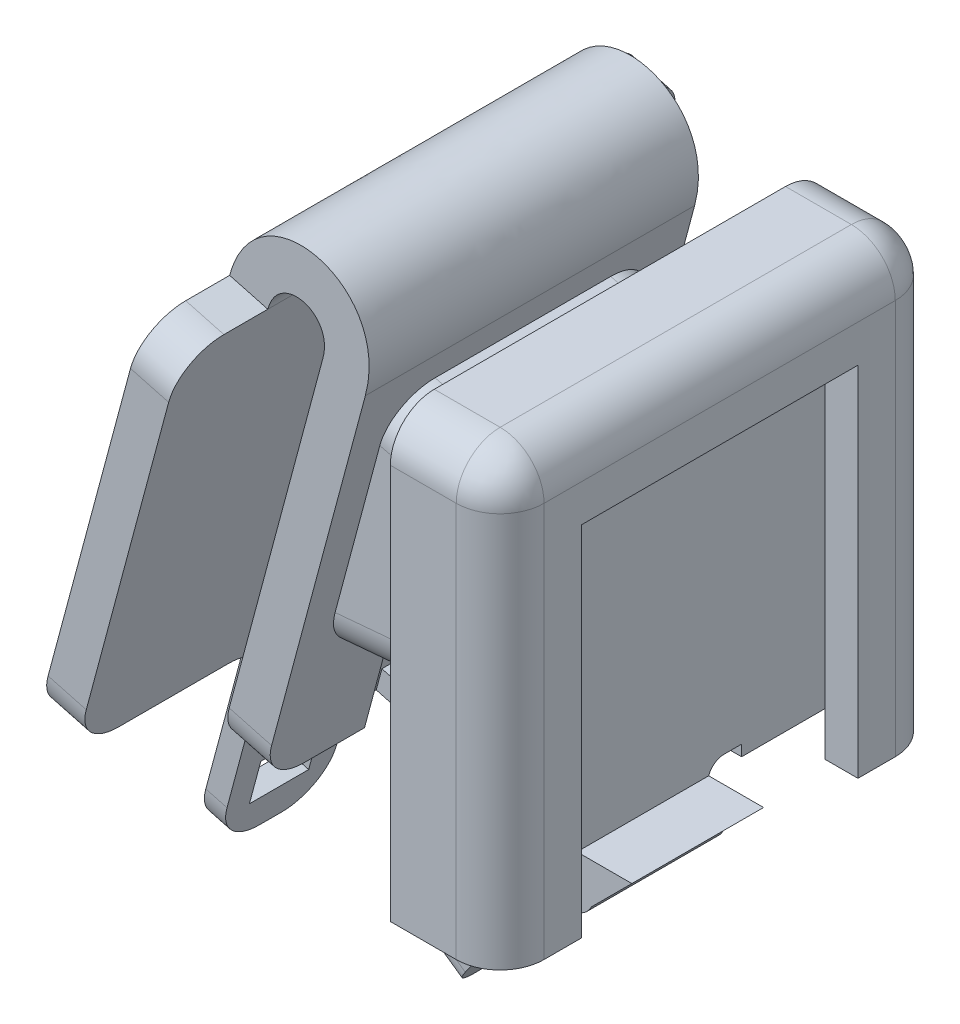
SolidWorks part; units mm, degrees
ref_plane "Front Plane" through (0, 0, 0) normal (0, 0, 1) x (1, 0, 0)
ref_plane "Top Plane" through (0, 0, 0) normal (0, 1, 0) x (1, 0, 0)
ref_plane "Right Plane" through (0, 0, 0) normal (1, 0, 0) x (0, 0, -1)
ref_axis "Axis1" through (-33.0333, 0, 0) along (1, 0, 0)
ref_axis "Axis2" through (0, 24.5224, 0) along (0, -1, 0)
ref_axis "Axis3" through (0, 0, -30.7663) along (0, 0, 1)
sketch "Sketch1" plane through (0, 0, 0) normal (1, 0, 0) x (0, 0, -1)
  line L2 (-10, -10) -> (-10, 10)
  line L4 (10, -10) -> (10, 10)
  line L5 (-10, -10) -> (10, 10) construction
  line L6 (-10, 10) -> (10, -10) construction
  line L8 (-10, 10) -> (10, 10)
  line L19 (0, -10) -> (0, 0) construction
  line L20 (-10, -10) -> (-4.5, -10)
  line L21 (-4.5, -10) -> (-4.5, -9.5)
  line L22 (-4.5, -9.5) -> (-3, -9.5)
  line L23 (-3, -9.5) -> (-3, -10)
  line L24 (-3, -10) -> (3, -10)
  line L25 (3, -10) -> (3, -9.5)
  line L26 (3, -9.5) -> (4.5, -9.5)
  line L27 (4.5, -9.5) -> (4.5, -10)
  line L28 (4.5, -10) -> (10, -10)
  point P0 (0, 0)
  point P25 (0, -10)
  dimension "D1" = 20
  dimension "D2" = 20
  dimension "D6" = 9
  dimension "D7" = 1.5
  dimension "D8" = 0.5
extrude "Boss-Extrude1" add sketch "Sketch1" along normal blind 1.5
fillet "Fillet7" radius 0.75 2 edges at (0.75, -9.5, -3) (0.75, -9.5, 3)
sketch "Sketch3" plane through (1.5, 0, 0) normal (1, 0, 0) x (0, 0, -1)
  line L2 (-10, 10) -> (-10, -10)
  line L4 (10, 10) -> (10, -10)
  line L6 (-8.5, 8.5) -> (-8.5, -10)
  line L10 (8.5, -10) -> (8.5, 8.5)
  line L14 (-10, -10) -> (-4.5, -10) construction
  line L15 (-10, -10) -> (-8.5, -10)
  line L16 (4.5, -10) -> (10, -10) construction
  line L17 (8.5, -10) -> (10, -10)
  line L18 (-8.5, 8.5) -> (8.5, 8.5)
  line L19 (0, 8.5) -> (0, 10) construction
  line L20 (10, 10) -> (-10, 10) construction
  line L21 (-10, 10) -> (10, 10)
  dimension "D1" = 1.5
  dimension "D2" = 1.5
extrude "Boss-Extrude2" add sketch "Sketch3" along normal blind 2
sketch "Sketch5" plane through (3.5, 0, 0) normal (1, 0, 0) x (0, 0, -1)
  line L0 (-10, 10) -> (-10, -10)
  line L2 (10, -10) -> (10, 10)
  line L5 (6.3, 6.3) -> (6.3, -10)
  line L7 (-6.3, -10) -> (-6.3, 6.3)
  line L12 (-8.5, -10) -> (-4.5, -10) construction
  line L13 (4.5, -10) -> (8.5, -10) construction
  line L14 (10, -10) -> (10, 10) construction
  line L15 (-10, 10) -> (10, 10)
  line L16 (6.3, 6.3) -> (-6.3, 6.3)
  line L17 (-6.3, -10) -> (-10, -10)
  line L18 (6.3, -10) -> (10, -10)
  line L19 (0, 6.3) -> (0, 10) construction
  dimension "D1" = 3.7
extrude "Boss-Extrude3" add sketch "Sketch5" along normal blind 1.5
sketch "Sketch9" plane through (0, 0, 0) normal (0, 0, 1) x (1, 0, 0)
  line L14 (0, -10) -> (4, -10)
  line L15 (5, -10) -> (0, -10) construction
  line L16 (4, -10) -> (2.1589, -11.8411)
  line L17 (2.1589, -11.8411) -> (2.1589, -12.4078)
  line L18 (2.1589, -12.4078) -> (-0.1693, -12.4078)
  line L19 (-0.1693, -12.4078) -> (-4.1619, -18.1099)
  line L20 (-4.1619, -18.1099) -> (-5.8002, -16.9628)
  line L21 (-5.8002, -16.9628) -> (-0.9248, -10)
  line L24 (-0.9248, -10) -> (0, -10)
  dimension "D2" = 0.9248
  dimension "D8" = 4
  dimension "D9" = 45
  dimension "D10" = 125
  dimension "D13" = 8.5
  dimension "D14" = 2
extrude "Boss-Extrude5" add sketch "Sketch9" along normal up to vertex (3 mm away) and the other way up to vertex (3 mm away) contours L14 L16 L17 L18 L19 L20 L21 L24 up to point (1.5, -10, 3) other way up to point (1.5, -10, -3)
sketch "Sketch6" plane through (0, 0, 0) normal (0, 0, 1) x (1, 0, 0)
  line L0 (0, 0) -> (-7, 0) construction
  line L1 (0, 10) -> (0, -10) construction
  line L2 (-7, 0) -> (-7, -1) construction
  line L3 (-4.6059, 7.9348) -> (-9.3941, -9.9348) construction
  line L4 (-10.36, -9.676) -> (-8.4282, -10.1936)
  line L5 (-10.36, -9.676) -> (-5.5718, 8.1936)
  line L6 (-5.5718, 8.1936) -> (-3.64, 7.676)
  line L7 (-8.4282, -10.1936) -> (-3.64, 7.676)
  dimension "D1" = 2
  dimension "D2" = 9.25
  dimension "D3" = 75
  dimension "D4" = 1
  dimension "D5" = 7
  dimension "D6" = 9.25
extrude "Boss-Extrude4" add sketch "Sketch6" along normal blind 7.5 and the other way blind 7.5 separate body
sketch "Sketch7" plane through (-5.3152, 1.4242, 0) normal (0.9659, -0.2588, 0) x (0, 0, -1)
  line L0 (0, -12.0277) -> (0, 6.4723) construction
  line L1 (7.5, -12.0277) -> (-7.5, -12.0277) construction
  line L2 (7.5, 6.4723) -> (-7.5, 6.4723) construction
  line L3 (-6, -6.7777) -> (6, -6.7777)
  line L4 (-6, -6.7777) -> (-6, 5.2223)
  line L5 (-6, 5.2223) -> (6, 5.2223)
  line L6 (6, -6.7777) -> (6, 5.2223)
  line L7 (-6, -6.7777) -> (6, 5.2223) construction
  line L8 (-6, 5.2223) -> (6, -6.7777) construction
  point P8 (0, -0.7777)
  point P13 (0, -2.7777)
  dimension "D1" = 12
  dimension "D2" = 12
  dimension "D3" = 2
sketch "Sketch8" plane through (0, 0, 0) normal (-1, 0, 0) x (0, 0, 1)
  line L0 (0, 0) -> (0, 0.5) construction
  line L2 (-6, -4.5) -> (6, -4.5)
  line L3 (-6, -4.5) -> (-6, 5.5)
  line L4 (-6, 5.5) -> (6, 5.5)
  line L5 (6, -4.5) -> (6, 5.5)
  line L6 (-6, -4.5) -> (6, 5.5) construction
  line L7 (-6, 5.5) -> (6, -4.5) construction
  dimension "D1" = 12
  dimension "D2" = 0.5
  dimension "D3" = 10
loft "Loft1" add profiles "Sketch7", "Sketch8" connector at (-7.0694, -5.1225, 6) connector at (0, -4.5, 6)
ref_plane "Plane1" through (1.3516, 5.0444, 0) normal (0.2588, 0.9659, 0) x (0, 0, 1)
ref_plane "Plane2" through (-9.7584, 2.6148, 0) normal (-0.9659, 0.2588, 0) x (0, 0, 1)
sketch "Sketch11" plane through (-9.7584, 2.6148, 0) normal (-0.9659, 0.2588, 0) x (0, 0, 1)
  line L0 (0, 6.4723) -> (0, -12.0277) construction
  line L1 (-11.5, -12.0277) -> (-4, -12.0277)
  line L2 (-11.5, -12.0277) -> (-11.5, 6.4723)
  line L3 (-11.5, 6.4723) -> (11.5, 6.4723)
  line L4 (11.5, -12.0277) -> (11.5, 6.4723)
  line L5 (-11.5, -12.0277) -> (11.5, 6.4723) construction
  line L6 (-11.5, 6.4723) -> (11.5, -12.0277) construction
  line L7 (-7.5, 6.4723) -> (7.5, 6.4723) construction
  line L8 (-7.5, -12.0277) -> (7.5, -12.0277) construction
  line L12 (-4, -12.0277) -> (11.5, -12.0277)
  point P0 (0, 0)
  point P5 (0, -2.7777)
  point P13 (0, -2.7777)
  point P19 (0, -14.4137)
  dimension "D1" = 18.5
  dimension "D2" = 23
extrude "Boss-Extrude6" add sketch "Sketch11" along normal blind 1.8 separate body
sketch "Sketch12" plane through (0, 0, 7.5) normal (0, 0, 1) x (1, 0, 0)
  line L0 (-14.6101, -8.5372) -> (-9.8219, 9.3324) construction
  line L1 (-5.5718, 8.1936) -> (-10.36, -9.676) construction
  line L2 (-9.8219, 9.3324) -> (-8.0833, 8.8666)
  line L3 (-5.5718, 8.1936) -> (-3.64, 7.676)
  line L4 (-8.7898, 13.1845) -> (-10.8004, 5.6806) construction
  line L5 (-8.4282, -10.1936) -> (-3.64, 7.676) construction
  line L6 (-4.695, 3.7386) -> (-2.6547, 11.3531) construction
  line L7 (-5.9975, 6.6051) -> (-5.1773, 9.6661) construction
  line L8 (-12.8714, -9.0031) -> (-8.0833, 8.8666) construction
  line L9 (-7.6628, 10.4359) -> (-8.4847, 7.3682) construction
  spline S0 degree 3 poles (-8.0833, 8.8666) (-7.5695, 10.7838) (-5.0592, 10.1068) (-5.5718, 8.1936) knots 0 0 0 0 1 1 1 1
  spline S1 degree 3 poles (-9.8219, 9.3324) (-8.5701, 14.0044) (-2.3648, 12.435) (-3.64, 7.676) knots 0 0 0 0 1 1 1 1
extrude "Boss-Extrude7" add sketch "Sketch12" against normal up to surface (15 mm away) up to face at (-7, -1, -7.5)
sketch "Sketch18" plane through (-3.113, -11.6178, 0) normal (-0.2588, -0.9659, 0) x (0.9659, -0.2588, 0)
  line L1 (-6.5027, 2.75) -> (-5.5027, 2.75)
  line L2 (-6.5027, 2.75) -> (-6.5027, -2.75)
  line L3 (-6.5027, -2.75) -> (-5.5027, -2.75)
  line L4 (-5.5027, 2.75) -> (-5.5027, -2.75)
  line L5 (-5.5027, -7.5) -> (-5.5027, 7.5) construction
  line L6 (-5.5027, -7.5) -> (-5.5027, 7.5) construction
  line L7 (-6.5027, 2.75) -> (-7.5027, 2.75) construction
  line L8 (-7.5027, -7.5) -> (-7.5027, 7.5) construction
  point P2 (-5.5027, 0)
  point P3 (-5.5027, 0)
  dimension "D1" = 5.5
  dimension "D2" = 1
extrude "Cut-Extrude2" cut sketch "Sketch18" against normal blind 5
fillet "Fillet8" radius 2 1 edges at (-8.1, -5.1052, 0)
sketch "Sketch14" plane through (-6.2811, 1.683, 0) normal (0.9659, -0.2588, 0) x (0, 0, -1)
  line L0 (-2.75, -12.0277) -> (2.75, -12.0277) construction
  line L1 (-1.25, -12.0277) -> (1.25, -12.0277)
  line L2 (-1.25, -12.0277) -> (-1.25, -11.0277)
  line L3 (-1.25, -11.0277) -> (1.25, -11.0277)
  line L4 (1.25, -12.0277) -> (1.25, -11.0277)
  point P4 (0, -12.0277)
  point P7 (0, -12.0277)
  dimension "D1" = 1
  dimension "D2" = 2.5
extrude "Boss-Extrude9" add sketch "Sketch14" along normal blind 1.15
sketch "Sketch16" plane through (-5.1703, 1.3854, 0) normal (0.9659, -0.2588, 0) x (0, 0, -1)
  line L0 (1.25, -11.0277) -> (-1.25, -11.0277) construction
  line L1 (-1.25, -12.0277) -> (1.25, -12.0277)
  line L2 (-1.25, -12.0277) -> (-1.25, -9.0277)
  line L3 (-1.25, -9.0277) -> (1.25, -9.0277)
  line L4 (1.25, -12.0277) -> (1.25, -9.0277)
  dimension "D1" = 2
extrude "Boss-Extrude11" add sketch "Sketch16" along normal blind 1
ref_plane "Plane4" through (0, 0, 0) normal (0, 0, 1) x (1, 0, 0)
sketch "Sketch15" plane through (-9.7584, 2.6148, 0) normal (0.9659, -0.2588, 0) x (0, 0, -1)
  line L0 (-11.5, -12.0277) -> (11.5, -12.0277) construction
  line L1 (0, -20.5277) -> (0, -22.0277) construction
  line L2 (-2.5, -12.0277) -> (2.5, -12.0277)
  line L3 (-2.5, -12.0277) -> (-2.5, -22.0277)
  line L4 (-2.5, -22.0277) -> (2.5, -22.0277)
  line L5 (2.5, -12.0277) -> (2.5, -22.0277)
  line L6 (-1.35, -20.5277) -> (1.35, -20.5277)
  line L7 (-1.35, -20.5277) -> (-1.35, -18.5277)
  line L8 (-1.35, -18.5277) -> (1.35, -18.5277)
  line L9 (1.35, -20.5277) -> (1.35, -18.5277)
  point P8 (0, -12.0277)
  point P9 (0, -12.0277)
  dimension "D1" = 5
  dimension "D2" = 10
  dimension "D3" = 2.7
  dimension "D4" = 2
  dimension "D5" = 1.5
extrude "Boss-Extrude10" add sketch "Sketch15" against normal blind 1
fillet "Fillet2" radius 1 5 edges at (2.1589, -12.4078, 0) (-0.1693, -12.4078, 0) (-4.9811, -17.5364, -3) (-4.9811, -17.5364, 3) (-0.9248, -10, 0)
fillet "Fillet3" radius 2 4 edges at (-15.9426, -18.5329, -2.5) (-15.9426, -18.5329, 2.5) (-13.3544, -8.8737, -2.5) (-13.3544, -8.8737, 2.5)
fillet "Fillet4" radius 2 15 edges at (5, 0, 10) (5, 10, 0) (5, 0, -10) (2.5, 10, -10) (2.5, 10, 10) (-8.9526, 9.0995, -11.5) (-13.7407, -8.7701, -11.5) (-13.7407, -8.7701, 11.5) (-8.9526, 9.0995, 11.5) (-9.3941, -9.9348, -7.5) (-9.3941, -9.9348, 7.5)
fillet "Fillet5" radius 1.55 1 edges at (-7.3173, -10.4913, 0)
